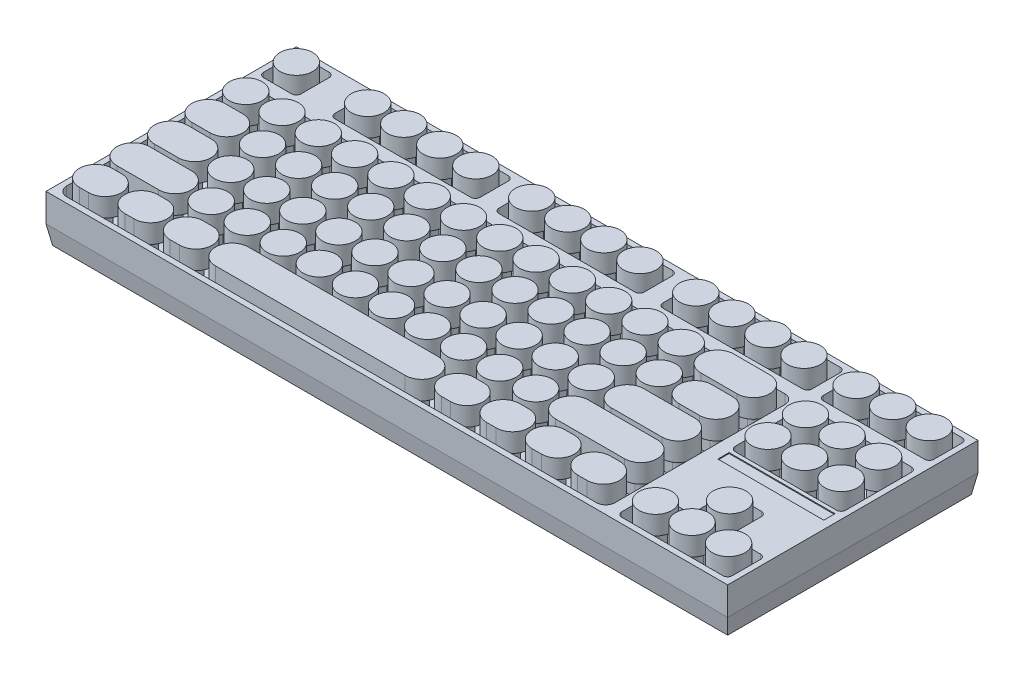
SolidWorks part; units mm, degrees
ref_plane "Front Plane" through (0, 0, 0) normal (0, 0, 1) x (1, 0, 0)
ref_plane "Top Plane" through (0, 0, 0) normal (0, 1, 0) x (1, 0, 0)
ref_plane "Right Plane" through (0, 0, 0) normal (1, 0, 0) x (0, 0, -1)
sketch "Sketch1" plane through (0, 0, 0) normal (0, 1, 0) x (1, 0, 0)
  line L1 (180, 65) -> (-180, 65)
  line L2 (180, 65) -> (180, -65)
  line L3 (180, -65) -> (-180, -65)
  line L4 (-180, 65) -> (-180, -65)
  line L5 (180, 65) -> (-180, -65) construction
  line L6 (180, -65) -> (-180, 65) construction
  point P0 (0, 0)
  dimension "D1" = 360
  dimension "D2" = 130
extrude "Boss-Extrude1" add sketch "Sketch1" along normal blind 10
draft "Draft1" type of draft neutral plane draft angle 10 faces to draft 4 face at (180, 5, 0) face at (0, 5, -65) face at (-180, 5, 0) face at (0, 5, 65) neutral plane through (0, 0, 0) neutral plane normal (0, -1, 0) parameters "D1"=10
sketch "Sketch2" plane through (0, 10, 0) normal (0, 1, 0) x (1, 0, 0)
  line L0 (111.2633, 63.7633) -> (36.7667, 63.7633)
  line L1 (113.7633, 61.2633) -> (113.7633, 46.2633)
  line L2 (111.2633, 43.7633) -> (36.7667, 43.7633)
  line L3 (34.2667, 61.2633) -> (34.2667, 46.2633)
  line L4 (176.2633, 63.7633) -> (122.2633, 63.7633)
  line L5 (176.2633, -43.7633) -> (122.2633, -43.7633) construction
  line L6 (178.7633, -46.2633) -> (178.7633, -61.2633)
  line L7 (176.2633, -63.7633) -> (122.2633, -63.7633)
  line L8 (119.7633, -46.2633) -> (119.7633, -61.2633)
  line L9 (178.7633, -43.7633) -> (119.7633, -63.7633) construction
  line L10 (178.7633, -63.7633) -> (119.7633, -43.7633) construction
  line L11 (156.7633, -23.7633) -> (141.7633, -23.7633)
  line L12 (159.2633, -26.2633) -> (159.2633, -41.2633)
  line L13 (159.2633, -43.7633) -> (139.2633, -43.7633) construction
  line L14 (139.2633, -26.2633) -> (139.2633, -41.2633)
  line L15 (159.2633, -23.7633) -> (139.2633, -43.7633) construction
  line L16 (-178.7633, 66.7633) -> (-178.7633, -66.7633)
  line L17 (-178.7633, 31.7633) -> (-178.7633, -58.7633)
  line L18 (159.2633, -43.7633) -> (139.2633, -23.7633) construction
  line L19 (181.7633, 36.7633) -> (-181.7633, 36.7633)
  line L20 (108.7633, 36.7633) -> (-173.7633, 36.7633)
  line L21 (178.7633, 61.2633) -> (178.7633, 46.2633)
  line L22 (113.7633, -66.7633) -> (113.7633, 66.7633)
  line L23 (113.7633, -58.7633) -> (113.7633, 31.7633)
  line L24 (176.2633, 43.7633) -> (122.2633, 43.7633)
  line L25 (-181.7633, -63.7633) -> (181.7633, -63.7633)
  line L26 (-173.7633, -63.7633) -> (108.7633, -63.7633)
  line L27 (-181.7633, 66.7633) -> (-181.7633, -66.7633) construction
  line L28 (-161.2633, 63.7633) -> (-176.2633, 63.7633)
  line L29 (-158.7633, 61.2633) -> (-158.7633, 46.2633)
  line L30 (-161.2633, 43.7633) -> (-176.2633, 43.7633)
  line L31 (-178.7633, 61.2633) -> (-178.7633, 46.2633)
  line L32 (-158.7633, 63.7633) -> (-178.7633, 43.7633) construction
  line L33 (-158.7633, 43.7633) -> (-178.7633, 63.7633) construction
  line L34 (181.7633, 66.7633) -> (-181.7633, 66.7633) construction
  line L35 (-181.7633, -66.7633) -> (181.7633, -66.7633) construction
  line L36 (-65.7333, 63.7633) -> (-138.2333, 63.7633)
  line L37 (-63.2333, 61.2633) -> (-63.2333, 46.2633)
  line L38 (-65.7333, 43.7633) -> (-138.2333, 43.7633)
  line L39 (-140.7333, 61.2633) -> (-140.7333, 46.2633)
  line L40 (-63.2333, 63.7633) -> (-140.7333, 43.7633) construction
  line L41 (-63.2333, 43.7633) -> (-140.7333, 63.7633) construction
  line L42 (181.7633, -66.7633) -> (181.7633, 66.7633) construction
  line L43 (-181.7633, 66.7633) -> (-181.7633, -66.7633)
  line L44 (-181.7633, -66.7633) -> (181.7633, -66.7633)
  line L45 (181.7633, -66.7633) -> (181.7633, 66.7633)
  line L46 (181.7633, 66.7633) -> (-181.7633, 66.7633)
  line L47 (21.7667, 63.7633) -> (-50.7333, 63.7633)
  line L48 (24.2667, 61.2633) -> (24.2667, 46.2633)
  line L49 (21.7667, 43.7633) -> (-50.7333, 43.7633)
  line L50 (-53.2333, 61.2633) -> (-53.2333, 46.2633)
  line L51 (119.7633, 61.2633) -> (119.7633, 46.2633)
  line L52 (122.2633, -43.7633) -> (136.7633, -43.7633)
  line L53 (176.2633, 36.7633) -> (122.2633, 36.7633)
  line L54 (178.7633, 34.2633) -> (178.7633, -0.7367)
  line L55 (176.2633, -3.2367) -> (122.2633, -3.2367)
  line L56 (119.7633, 34.2633) -> (119.7633, -0.7367)
  line L57 (178.7633, 36.7633) -> (119.7633, -3.2367) construction
  line L58 (178.7633, -3.2367) -> (119.7633, 36.7633) construction
  line L59 (176.2633, -43.7633) -> (161.7633, -43.7633)
  arc A0 (108.7633, -63.7633) -> (113.7633, -58.7633) centre (108.7633, -58.7633) ccw
  arc A1 (113.7633, 31.7633) -> (108.7633, 36.7633) centre (108.7633, 31.7633) ccw
  arc A2 (-173.7633, -63.7633) -> (-178.7633, -58.7633) centre (-173.7633, -58.7633) cw
  arc A3 (-178.7633, 31.7633) -> (-173.7633, 36.7633) centre (-173.7633, 31.7633) cw
  arc A4 (178.7633, -61.2633) -> (176.2633, -63.7633) centre (176.2633, -61.2633) cw
  arc A5 (176.2633, -43.7633) -> (178.7633, -46.2633) centre (176.2633, -46.2633) cw
  arc A6 (122.2633, -43.7633) -> (119.7633, -46.2633) centre (122.2633, -46.2633) ccw
  arc A7 (122.2633, -63.7633) -> (119.7633, -61.2633) centre (122.2633, -61.2633) cw
  arc A8 (156.7633, -23.7633) -> (159.2633, -26.2633) centre (156.7633, -26.2633) cw
  arc A9 (141.7633, -23.7633) -> (139.2633, -26.2633) centre (141.7633, -26.2633) ccw
  arc A10 (178.7633, -0.7367) -> (176.2633, -3.2367) centre (176.2633, -0.7367) cw
  arc A11 (122.2633, -3.2367) -> (119.7633, -0.7367) centre (122.2633, -0.7367) cw
  arc A12 (122.2633, 36.7633) -> (119.7633, 34.2633) centre (122.2633, 34.2633) ccw
  arc A13 (176.2633, 36.7633) -> (178.7633, 34.2633) centre (176.2633, 34.2633) cw
  arc A14 (178.7633, 46.2633) -> (176.2633, 43.7633) centre (176.2633, 46.2633) cw
  arc A15 (176.2633, 63.7633) -> (178.7633, 61.2633) centre (176.2633, 61.2633) cw
  arc A16 (122.2633, 63.7633) -> (119.7633, 61.2633) centre (122.2633, 61.2633) ccw
  arc A17 (122.2633, 43.7633) -> (119.7633, 46.2633) centre (122.2633, 46.2633) cw
  arc A18 (113.7633, 46.2633) -> (111.2633, 43.7633) centre (111.2633, 46.2633) cw
  arc A19 (111.2633, 63.7633) -> (113.7633, 61.2633) centre (111.2633, 61.2633) cw
  arc A20 (36.7667, 63.7633) -> (34.2667, 61.2633) centre (36.7667, 61.2633) ccw
  arc A21 (36.7667, 43.7633) -> (34.2667, 46.2633) centre (36.7667, 46.2633) cw
  arc A22 (24.2667, 46.2633) -> (21.7667, 43.7633) centre (21.7667, 46.2633) cw
  arc A23 (21.7667, 63.7633) -> (24.2667, 61.2633) centre (21.7667, 61.2633) cw
  arc A24 (-50.7333, 43.7633) -> (-53.2333, 46.2633) centre (-50.7333, 46.2633) cw
  arc A25 (-50.7333, 63.7633) -> (-53.2333, 61.2633) centre (-50.7333, 61.2633) ccw
  arc A26 (-63.2333, 46.2633) -> (-65.7333, 43.7633) centre (-65.7333, 46.2633) cw
  arc A27 (-65.7333, 63.7633) -> (-63.2333, 61.2633) centre (-65.7333, 61.2633) cw
  arc A28 (-138.2333, 43.7633) -> (-140.7333, 46.2633) centre (-138.2333, 46.2633) cw
  arc A29 (-138.2333, 63.7633) -> (-140.7333, 61.2633) centre (-138.2333, 61.2633) ccw
  arc A30 (-158.7633, 46.2633) -> (-161.2633, 43.7633) centre (-161.2633, 46.2633) cw
  arc A31 (-176.2633, 43.7633) -> (-178.7633, 46.2633) centre (-176.2633, 46.2633) cw
  arc A32 (-176.2633, 63.7633) -> (-178.7633, 61.2633) centre (-176.2633, 61.2633) ccw
  arc A33 (-161.2633, 63.7633) -> (-158.7633, 61.2633) centre (-161.2633, 61.2633) cw
  arc A34 (136.7633, -43.7633) -> (139.2633, -41.2633) centre (136.7633, -41.2633) ccw
  arc A35 (159.2633, -41.2633) -> (161.7633, -43.7633) centre (161.7633, -41.2633) ccw
  point P22 (-168.7633, 53.7633)
  point P30 (-101.9833, 53.7633)
  point P42 (149.2633, -53.7633)
  point P47 (149.2633, -33.7633)
  point P57 (149.2633, 16.7633)
  point P94 (178.7633, 43.7633)
  point P97 (178.7633, 63.7633)
  point P104 (113.7633, 43.7633)
  point P107 (113.7633, 63.7633)
  point P110 (34.2667, 63.7633)
  point P115 (24.2667, 43.7633)
  point P118 (24.2667, 63.7633)
  point P123 (-53.2333, 63.7633)
  dimension "D5" = 5
  dimension "D34" = 2.5
  dimension "D35" = 2.5
  dimension "D6" = 20
  dimension "D7" = 3
  dimension "D8" = 3
  dimension "D9" = 18.03
  dimension "D10" = 77.5
  dimension "D11" = 20
  dimension "D12" = 3
  dimension "D13" = 10
  dimension "D14" = 3
  dimension "D15" = 20
  dimension "D16" = 77.5
  dimension "D18" = 20
  dimension "D19" = 3
  dimension "D20" = 10
  dimension "D21" = 3
  dimension "D22" = 6
  dimension "D23" = 3
  dimension "D24" = 20
  dimension "D25" = 20
  dimension "D26" = 20
  dimension "D28" = 20
  dimension "D29" = 3
  dimension "D30" = 3
  dimension "D31" = 40
  dimension "D32" = 3
  dimension "D33" = 6
  dimension "D1" = 3
  dimension "D2" = 30
  dimension "D3" = 68
  dimension "D4" = 3
extrude "Boss-Extrude2" add sketch "Sketch2" along normal blind 15
sketch "Sketch3" plane through (0, 10, 0) normal (0, 1, 0) x (1, 0, 0)
  line L0 (-178.031, 63.031) -> (-159.4955, 44.4955) construction
  line L1 (-178.031, 44.4955) -> (-159.4955, 63.031) construction
  line L2 (178.7633, 46.2633) -> (178.7633, 61.2633) construction
  line L3 (-63.2333, 46.2633) -> (-63.2333, 61.2633) construction
  line L4 (176.2633, 36.7633) -> (122.2633, 36.7633) construction
  line L5 (-140.7333, 61.2633) -> (-140.7333, 46.2633) construction
  line L6 (178.7633, 16.7633) -> (119.7633, 16.7633) construction
  line L7 (178.7633, -0.7367) -> (178.7633, 34.2633) construction
  line L8 (119.7633, 34.2633) -> (119.7633, -0.7367) construction
  line L9 (90.9667, 6.7633) -> (101.9567, 6.7633) construction
  line L10 (-168.7633, 6.7633) -> (-159.0233, 6.7633) construction
  line L11 (-168.7633, 9.7633) -> (-159.0233, 9.7633)
  line L12 (-168.7633, 3.7633) -> (-159.0233, 3.7633)
  line L13 (-168.7633, -13.2367) -> (-156.0233, -13.2367) construction
  line L14 (-53.2333, 61.2633) -> (-53.2333, 46.2633) construction
  line L15 (34.2667, 61.2633) -> (34.2667, 46.2633) construction
  line L16 (119.7633, 61.2633) -> (119.7633, 46.2633) construction
  line L17 (-168.7633, -10.2367) -> (-156.0233, -10.2367)
  line L18 (-168.7633, -16.2367) -> (-156.0233, -16.2367)
  line L19 (-168.7633, -33.2367) -> (-146.4083, -33.2367) construction
  line L20 (-168.7633, -30.2367) -> (-146.4083, -30.2367)
  line L21 (-168.7633, -36.2367) -> (-146.4083, -36.2367)
  line L22 (82.7267, 26.7633) -> (101.9567, 26.7633) construction
  line L23 (82.7267, 29.7633) -> (101.9567, 29.7633)
  line L24 (82.7267, 23.7633) -> (101.9567, 23.7633)
  line L25 (90.9667, 9.7633) -> (101.9567, 9.7633)
  line L26 (90.9667, 3.7633) -> (101.9567, 3.7633)
  line L27 (74.7367, -13.2367) -> (101.9567, -13.2367) construction
  line L28 (74.7367, -10.2367) -> (101.9567, -10.2367)
  line L29 (74.7367, -16.2367) -> (101.9567, -16.2367)
  line L30 (65.1217, -33.2367) -> (101.9567, -33.2367) construction
  line L31 (65.1217, -30.2367) -> (101.9567, -30.2367)
  line L32 (65.1217, -36.2367) -> (101.9567, -36.2367)
  line L33 (-168.7633, -53.2367) -> (-163.7633, -53.2367) construction
  line L34 (-168.7633, -50.2367) -> (-163.7633, -50.2367)
  line L35 (-168.7633, -56.2367) -> (-163.7633, -56.2367)
  line L36 (-144.5333, -53.2367) -> (-139.5333, -53.2367) construction
  line L37 (-144.5333, -50.2367) -> (-139.5333, -50.2367)
  line L38 (-144.5333, -56.2367) -> (-139.5333, -56.2367)
  line L39 (-120.3033, -53.2367) -> (-115.3033, -53.2367) construction
  line L40 (-120.3033, -50.2367) -> (-115.3033, -50.2367)
  line L41 (-120.3033, -56.2367) -> (-115.3033, -56.2367)
  line L42 (96.9567, -53.2367) -> (101.9567, -53.2367) construction
  line L43 (96.9567, -50.2367) -> (101.9567, -50.2367)
  line L44 (96.9567, -56.2367) -> (101.9567, -56.2367)
  line L45 (72.7267, -50.2367) -> (77.7267, -50.2367)
  line L46 (72.7267, -56.2367) -> (77.7267, -56.2367)
  line L47 (72.7267, -53.2367) -> (77.7267, -53.2367) construction
  line L48 (48.4967, -50.2367) -> (53.4967, -50.2367)
  line L49 (48.4967, -56.2367) -> (53.4967, -56.2367)
  line L50 (48.4967, -53.2367) -> (53.4967, -53.2367) construction
  line L51 (24.2667, -50.2367) -> (29.2667, -50.2367)
  line L52 (24.2667, -56.2367) -> (29.2667, -56.2367)
  line L53 (24.2667, -53.2367) -> (29.2667, -53.2367) construction
  line L54 (-96.0733, -53.2367) -> (5.0367, -53.2367) construction
  line L55 (-96.0733, -50.2367) -> (5.0367, -50.2367)
  line L56 (-96.0733, -56.2367) -> (5.0367, -56.2367)
  arc A0 (-176.2633, 63.7633) -> (-178.7633, 61.2633) centre (-176.2633, 61.2633) ccw construction
  arc A1 (-161.2633, 43.7633) -> (-158.7633, 46.2633) centre (-161.2633, 46.2633) ccw construction
  arc A2 (-178.7633, 46.2633) -> (-176.2633, 43.7633) centre (-176.2633, 46.2633) ccw construction
  arc A3 (-158.7633, 61.2633) -> (-161.2633, 63.7633) centre (-161.2633, 61.2633) ccw construction
  circle A4 centre (-168.7633, 53.7633) radius 4.5
  circle A5 centre (-130.7333, 53.7633) radius 4.5
  circle A6 centre (-111.5083, 53.7633) radius 4.5
  circle A7 centre (-92.4583, 53.7633) radius 4.5
  circle A8 centre (-73.2333, 53.7633) radius 4.5
  circle A43 centre (-43.2333, 53.7633) radius 4.5
  circle A44 centre (44.2667, 53.7633) radius 4.5
  circle A45 centre (129.7633, 53.7633) radius 4.5
  circle A46 centre (-24.0033, 53.7633) radius 4.5
  circle A47 centre (-4.7733, 53.7633) radius 4.5
  circle A48 centre (14.4567, 53.7633) radius 4.5
  circle A49 centre (63.4967, 53.7633) radius 4.5
  circle A50 centre (82.7267, 53.7633) radius 4.5
  circle A51 centre (101.9567, 53.7633) radius 4.5
  circle A52 centre (168.7633, 53.7633) radius 4.5
  circle A53 centre (149.2633, 53.7633) radius 4.5
  circle A54 centre (129.7633, 26.7633) radius 4.5
  circle A55 centre (149.2633, 26.7633) radius 4.5
  circle A56 centre (168.7633, 26.7633) radius 4.5
  circle A57 centre (168.7633, 6.7633) radius 4.5
  circle A58 centre (149.2633, 6.7633) radius 4.5
  circle A59 centre (129.7633, 6.7633) radius 4.5
  circle A60 centre (63.4967, 26.7633) radius 4.5
  circle A61 centre (44.1417, 26.7633) radius 4.5
  circle A62 centre (24.7867, 26.7633) radius 4.5
  circle A63 centre (5.4317, 26.7633) radius 4.5
  circle A64 centre (-13.9233, 26.7633) radius 4.5
  circle A65 centre (-33.2783, 26.7633) radius 4.5
  circle A66 centre (-52.6333, 26.7633) radius 4.5
  circle A67 centre (-71.9883, 26.7633) radius 4.5
  circle A68 centre (-91.3433, 26.7633) radius 4.5
  circle A69 centre (-110.6983, 26.7633) radius 4.5
  circle A70 centre (-130.0533, 26.7633) radius 4.5
  circle A71 centre (-149.4083, 26.7633) radius 4.5
  circle A72 centre (-168.7633, 26.7633) radius 4.5
  circle A73 centre (129.7633, -53.2367) radius 4.5
  circle A74 centre (149.2633, -53.2367) radius 4.5
  circle A75 centre (168.7633, -53.2367) radius 4.5
  circle A76 centre (149.2633, -33.2367) radius 4.5
  circle A78 centre (-139.7933, 6.7633) radius 4.5
  circle A90 centre (-120.5633, 6.7633) radius 4.5
  circle A91 centre (-101.3333, 6.7633) radius 4.5
  circle A92 centre (-82.1033, 6.7633) radius 4.5
  circle A93 centre (-62.8733, 6.7633) radius 4.5
  circle A94 centre (-43.6433, 6.7633) radius 4.5
  circle A95 centre (-24.4133, 6.7633) radius 4.5
  circle A96 centre (-5.1833, 6.7633) radius 4.5
  circle A97 centre (14.0467, 6.7633) radius 4.5
  circle A98 centre (33.2767, 6.7633) radius 4.5
  circle A99 centre (52.5067, 6.7633) radius 4.5
  circle A100 centre (71.7367, 6.7633) radius 4.5
  circle A101 centre (-136.7933, -13.2367) radius 4.5
  circle A102 centre (-117.5633, -13.2367) radius 4.5
  circle A103 centre (-98.3333, -13.2367) radius 4.5
  circle A104 centre (-79.1033, -13.2367) radius 4.5
  circle A105 centre (-59.8733, -13.2367) radius 4.5
  circle A106 centre (-40.6433, -13.2367) radius 4.5
  circle A107 centre (-21.4133, -13.2367) radius 4.5
  circle A108 centre (-2.1833, -13.2367) radius 4.5
  circle A109 centre (17.0467, -13.2367) radius 4.5
  circle A110 centre (36.2767, -13.2367) radius 4.5
  circle A111 centre (55.5067, -13.2367) radius 4.5
  circle A112 centre (-127.1783, -33.2367) radius 4.5
  circle A113 centre (-107.9483, -33.2367) radius 4.5
  circle A114 centre (-88.7183, -33.2367) radius 4.5
  circle A115 centre (-69.4883, -33.2367) radius 4.5
  circle A116 centre (-50.2583, -33.2367) radius 4.5
  circle A117 centre (-31.0283, -33.2367) radius 4.5
  circle A118 centre (-11.7983, -33.2367) radius 4.5
  circle A119 centre (7.4317, -33.2367) radius 4.5
  circle A120 centre (26.6617, -33.2367) radius 4.5
  circle A121 centre (45.8917, -33.2367) radius 4.5
  arc A122 (-168.7633, 9.7633) -> (-168.7633, 3.7633) centre (-168.7633, 6.7633) ccw
  arc A123 (-159.0233, 3.7633) -> (-159.0233, 9.7633) centre (-159.0233, 6.7633) ccw
  arc A124 (-168.7633, -10.2367) -> (-168.7633, -16.2367) centre (-168.7633, -13.2367) ccw
  arc A125 (-156.0233, -16.2367) -> (-156.0233, -10.2367) centre (-156.0233, -13.2367) ccw
  arc A126 (-168.7633, -30.2367) -> (-168.7633, -36.2367) centre (-168.7633, -33.2367) ccw
  arc A127 (-146.4083, -36.2367) -> (-146.4083, -30.2367) centre (-146.4083, -33.2367) ccw
  arc A128 (82.7267, 29.7633) -> (82.7267, 23.7633) centre (82.7267, 26.7633) ccw
  arc A129 (101.9567, 23.7633) -> (101.9567, 29.7633) centre (101.9567, 26.7633) ccw
  arc A130 (90.9667, 9.7633) -> (90.9667, 3.7633) centre (90.9667, 6.7633) ccw
  arc A131 (101.9567, 3.7633) -> (101.9567, 9.7633) centre (101.9567, 6.7633) ccw
  arc A132 (74.7367, -10.2367) -> (74.7367, -16.2367) centre (74.7367, -13.2367) ccw
  arc A133 (101.9567, -16.2367) -> (101.9567, -10.2367) centre (101.9567, -13.2367) ccw
  arc A134 (65.1217, -30.2367) -> (65.1217, -36.2367) centre (65.1217, -33.2367) ccw
  arc A135 (101.9567, -36.2367) -> (101.9567, -30.2367) centre (101.9567, -33.2367) ccw
  arc A136 (-168.7633, -50.2367) -> (-168.7633, -56.2367) centre (-168.7633, -53.2367) ccw
  arc A137 (-163.7633, -56.2367) -> (-163.7633, -50.2367) centre (-163.7633, -53.2367) ccw
  arc A138 (-144.5333, -50.2367) -> (-144.5333, -56.2367) centre (-144.5333, -53.2367) ccw
  arc A139 (-139.5333, -56.2367) -> (-139.5333, -50.2367) centre (-139.5333, -53.2367) ccw
  arc A140 (-120.3033, -50.2367) -> (-120.3033, -56.2367) centre (-120.3033, -53.2367) ccw
  arc A141 (-115.3033, -56.2367) -> (-115.3033, -50.2367) centre (-115.3033, -53.2367) ccw
  arc A142 (96.9567, -50.2367) -> (96.9567, -56.2367) centre (96.9567, -53.2367) ccw
  arc A143 (101.9567, -56.2367) -> (101.9567, -50.2367) centre (101.9567, -53.2367) ccw
  arc A144 (77.7267, -56.2367) -> (77.7267, -50.2367) centre (77.7267, -53.2367) ccw
  arc A145 (72.7267, -50.2367) -> (72.7267, -56.2367) centre (72.7267, -53.2367) ccw
  arc A146 (53.4967, -56.2367) -> (53.4967, -50.2367) centre (53.4967, -53.2367) ccw
  arc A147 (48.4967, -50.2367) -> (48.4967, -56.2367) centre (48.4967, -53.2367) ccw
  arc A148 (29.2667, -56.2367) -> (29.2667, -50.2367) centre (29.2667, -53.2367) ccw
  arc A149 (24.2667, -50.2367) -> (24.2667, -56.2367) centre (24.2667, -53.2367) ccw
  arc A150 (-96.0733, -50.2367) -> (-96.0733, -56.2367) centre (-96.0733, -53.2367) ccw
  arc A151 (5.0367, -56.2367) -> (5.0367, -50.2367) centre (5.0367, -53.2367) ccw
  point P113 (-163.8933, 6.7633)
  point P187 (-162.3933, -13.2367)
  point P194 (-166.2633, -53.2367)
  point P196 (-157.5858, -33.2367)
  point P203 (92.3417, 26.7633)
  point P212 (96.4617, 6.7633)
  point P220 (88.3467, -13.2367)
  point P227 (-142.0333, -53.2367)
  point P228 (99.4567, -53.2367)
  point P229 (83.5392, -33.2367)
  point P244 (-117.8033, -53.2367)
  point P257 (75.2267, -53.2367)
  point P265 (50.9967, -53.2367)
  point P272 (26.7667, -53.2367)
  point P280 (-45.5183, -53.2367)
  dimension "D1" = 9
  dimension "D30" = 3
  dimension "D34" = 3
  dimension "D35" = 3
  dimension "D37" = 3
  dimension "D39" = 3
  dimension "D41" = 3
  dimension "D43" = 3
  dimension "D44" = 3
  dimension "D46" = 3
  dimension "D48" = 3
  dimension "D51" = 3
  dimension "D2" = 10
  dimension "D3" = 10
  dimension "D4" = 19.225
  dimension "D5" = 19.225
  dimension "D6" = 10
  dimension "D7" = 10
  dimension "D8" = 10
  dimension "D9" = 19.23
  dimension "D10" = 19.23
  dimension "D11" = 10
  dimension "D12" = 19.5
  dimension "D13" = 10
  dimension "D14" = 19.5
  dimension "D15" = 3
  dimension "D16" = 4
  dimension "D17" = 20
  dimension "D18" = 10
  dimension "D19" = 3
  dimension "D20" = 13
  dimension "D21" = 20
  dimension "D22" = 9.615
  dimension "D23" = 19.23
  dimension "D24" = 12
  dimension "D26" = 3
  dimension "D25" = 20
  dimension "D27" = 19.23
  dimension "D29" = 9.615
  dimension "D31" = 9.615
  dimension "D32" = 19.23
  dimension "D33" = 19.23
  dimension "D36" = 19.23
  dimension "D38" = 19.23
  dimension "D40" = 19.23
  dimension "D42" = 19.23
  dimension "D45" = 5
  dimension "D47" = 19.23
  dimension "D49" = 5
  dimension "D50" = 19.23
  dimension "D52" = 19.23
  dimension "D53" = 19.23
  dimension "D28" = 11
extrude "Boss-Extrude3" add sketch "Sketch3" along normal blind 15
sketch "Sketch4" plane through (0, 25, 0) normal (0, 1, 0) x (1, 0, 0)
  line L0 (-168.7633, 6.7633) -> (-159.0233, 6.7633) construction
  line L3 (-168.7633, 15.5133) -> (-159.0233, 15.5133)
  line L4 (-168.7633, -1.9867) -> (-159.0233, -1.9867)
  line L5 (-168.7633, -13.2367) -> (-156.0233, -13.2367) construction
  line L6 (-168.7633, -4.4867) -> (-156.0233, -4.4867)
  line L7 (-168.7633, -21.9867) -> (-156.0233, -21.9867)
  line L8 (-168.7633, -33.2367) -> (-146.4083, -33.2367) construction
  line L9 (-168.7633, -24.4867) -> (-146.4083, -24.4867)
  line L10 (-168.7633, -41.9867) -> (-146.4083, -41.9867)
  line L11 (82.7267, 26.7633) -> (101.9567, 26.7633) construction
  line L12 (82.7267, 35.5133) -> (101.9567, 35.5133)
  line L13 (82.7267, 18.0133) -> (101.9567, 18.0133)
  line L14 (90.9667, 6.7633) -> (101.9567, 6.7633) construction
  line L15 (90.9667, 15.5133) -> (101.9567, 15.5133)
  line L16 (90.9667, -1.9867) -> (101.9567, -1.9867)
  line L17 (74.7367, -13.2367) -> (101.9567, -13.2367) construction
  line L18 (74.7367, -4.4867) -> (101.9567, -4.4867)
  line L19 (74.7367, -21.9867) -> (101.9567, -21.9867)
  line L20 (65.1217, -33.2367) -> (101.9567, -33.2367) construction
  line L21 (65.1217, -24.4867) -> (101.9567, -24.4867)
  line L22 (65.1217, -41.9867) -> (101.9567, -41.9867)
  line L23 (-168.7633, -53.2367) -> (-163.7633, -53.2367) construction
  line L24 (-168.7633, -44.4867) -> (-163.7633, -44.4867)
  line L25 (-168.7633, -61.9867) -> (-163.7633, -61.9867)
  line L26 (-144.5333, -61.9867) -> (-139.5333, -61.9867)
  line L29 (-144.5333, -44.4867) -> (-139.5333, -44.4867)
  line L30 (-144.5333, -53.2367) -> (-139.5333, -53.2367) construction
  line L31 (-120.3033, -61.9867) -> (-115.3033, -61.9867)
  line L32 (-120.3033, -44.4867) -> (-115.3033, -44.4867)
  line L33 (-120.3033, -53.2367) -> (-115.3033, -53.2367) construction
  line L34 (96.9567, -61.9867) -> (101.9567, -61.9867)
  line L35 (96.9567, -44.4867) -> (101.9567, -44.4867)
  line L36 (96.9567, -53.2367) -> (101.9567, -53.2367) construction
  line L37 (72.7267, -44.4867) -> (77.7267, -44.4867)
  line L38 (72.7267, -61.9867) -> (77.7267, -61.9867)
  line L39 (72.7267, -53.2367) -> (77.7267, -53.2367) construction
  line L40 (48.4967, -44.4867) -> (53.4967, -44.4867)
  line L41 (48.4967, -61.9867) -> (53.4967, -61.9867)
  line L42 (48.4967, -53.2367) -> (53.4967, -53.2367) construction
  line L43 (24.2667, -44.4867) -> (29.2667, -44.4867)
  line L44 (24.2667, -61.9867) -> (29.2667, -61.9867)
  line L45 (24.2667, -53.2367) -> (29.2667, -53.2367) construction
  line L46 (-96.0733, -53.2367) -> (5.0367, -53.2367) construction
  line L47 (-96.0733, -44.4867) -> (5.0367, -44.4867)
  line L48 (-96.0733, -61.9867) -> (5.0367, -61.9867)
  circle A0 centre (-168.7633, 53.7633) radius 8.75
  circle A1 centre (-130.7333, 53.7633) radius 8.75
  circle A2 centre (-111.5083, 53.7633) radius 8.75
  circle A3 centre (-92.2833, 53.7633) radius 8.75
  circle A4 centre (-73.0583, 53.7633) radius 8.75
  circle A5 centre (-43.2333, 53.7633) radius 8.75
  circle A6 centre (-24.0033, 53.7633) radius 8.75
  circle A7 centre (-4.7733, 53.7633) radius 8.75
  circle A8 centre (14.4567, 53.7633) radius 8.75
  circle A9 centre (44.2667, 53.7633) radius 8.75
  circle A10 centre (63.4967, 53.7633) radius 8.75
  circle A11 centre (82.7267, 53.7633) radius 8.75
  circle A12 centre (101.9567, 53.7633) radius 8.75
  circle A13 centre (129.7633, 53.7633) radius 8.75
  circle A16 centre (149.2633, 53.7633) radius 8.75
  circle A17 centre (168.7633, 53.7633) radius 8.75
  circle A18 centre (63.4967, 26.7633) radius 8.75
  circle A19 centre (44.1417, 26.7633) radius 8.75
  circle A20 centre (24.7867, 26.7633) radius 8.75
  circle A21 centre (5.4317, 26.7633) radius 8.75
  circle A22 centre (-13.9233, 26.7633) radius 8.75
  circle A23 centre (-33.2783, 26.7633) radius 8.75
  circle A24 centre (-52.6333, 26.7633) radius 8.75
  circle A25 centre (-71.9883, 26.7633) radius 8.75
  circle A26 centre (-91.3433, 26.7633) radius 8.75
  circle A27 centre (-110.6983, 26.7633) radius 8.75
  circle A28 centre (-130.0533, 26.7633) radius 8.75
  circle A29 centre (-149.4083, 26.7633) radius 8.75
  circle A30 centre (-168.7633, 26.7633) radius 8.75
  circle A31 centre (71.7367, 6.7633) radius 8.75
  circle A32 centre (52.5067, 6.7633) radius 8.75
  circle A33 centre (33.2767, 6.7633) radius 8.75
  circle A34 centre (14.0467, 6.7633) radius 8.75
  circle A35 centre (-5.1833, 6.7633) radius 8.75
  circle A36 centre (-24.4133, 6.7633) radius 8.75
  circle A37 centre (-43.6433, 6.7633) radius 8.75
  circle A38 centre (-62.8733, 6.7633) radius 8.75
  circle A39 centre (-82.1033, 6.7633) radius 8.75
  circle A40 centre (-101.3333, 6.7633) radius 8.75
  circle A41 centre (-120.5633, 6.7633) radius 8.75
  circle A42 centre (-139.7933, 6.7633) radius 8.75
  circle A44 centre (129.7633, 26.7633) radius 8.75
  circle A45 centre (129.7633, 6.7633) radius 8.75
  circle A48 centre (168.7633, 26.7633) radius 8.75
  circle A49 centre (168.7633, 6.7633) radius 8.75
  circle A50 centre (149.2633, 26.7633) radius 8.75 [skipped]
  circle A51 centre (149.2633, 6.7633) radius 8.75 [skipped]
  circle A52 centre (149.2633, 26.7633) radius 8.75
  circle A53 centre (149.2633, 6.7633) radius 8.75
  circle A54 centre (-159.0233, 6.7633) radius 8.75 [skipped]
  circle A55 centre (129.7633, -53.2367) radius 8.75
  circle A56 centre (149.2633, -33.2367) radius 8.75
  circle A57 centre (149.2633, -53.2367) radius 8.75
  circle A58 centre (168.7633, -53.2367) radius 8.75
  circle A59 centre (-136.7933, -13.2367) radius 8.75
  circle A60 centre (-117.5633, -13.2367) radius 8.75
  circle A61 centre (-98.3333, -13.2367) radius 8.75
  circle A62 centre (-79.1033, -13.2367) radius 8.75
  circle A63 centre (-59.8733, -13.2367) radius 8.75
  circle A64 centre (-40.6433, -13.2367) radius 8.75
  circle A65 centre (-21.4133, -13.2367) radius 8.75
  circle A66 centre (-2.1833, -13.2367) radius 8.75
  circle A67 centre (17.0467, -13.2367) radius 8.75
  circle A68 centre (36.2767, -13.2367) radius 8.75
  circle A69 centre (55.5067, -13.2367) radius 8.75
  circle A70 centre (-127.1783, -33.2367) radius 8.75
  circle A71 centre (-107.9483, -33.2367) radius 8.75
  circle A72 centre (-88.7183, -33.2367) radius 8.75
  circle A73 centre (-69.4883, -33.2367) radius 8.75
  circle A74 centre (-50.2583, -33.2367) radius 8.75
  circle A75 centre (-31.0283, -33.2367) radius 8.75
  circle A76 centre (-11.7983, -33.2367) radius 8.75
  circle A77 centre (7.4317, -33.2367) radius 8.75
  circle A78 centre (26.6617, -33.2367) radius 8.75
  circle A79 centre (45.8917, -33.2367) radius 8.75
  arc A82 (-168.7633, 15.5133) -> (-168.7633, -1.9867) centre (-168.7633, 6.7633) ccw
  arc A83 (-159.0233, -1.9867) -> (-159.0233, 15.5133) centre (-159.0233, 6.7633) ccw
  arc A84 (-168.7633, -4.4867) -> (-168.7633, -21.9867) centre (-168.7633, -13.2367) ccw
  arc A85 (-156.0233, -21.9867) -> (-156.0233, -4.4867) centre (-156.0233, -13.2367) ccw
  arc A86 (-168.7633, -24.4867) -> (-168.7633, -41.9867) centre (-168.7633, -33.2367) ccw
  arc A87 (-146.4083, -41.9867) -> (-146.4083, -24.4867) centre (-146.4083, -33.2367) ccw
  arc A88 (82.7267, 35.5133) -> (82.7267, 18.0133) centre (82.7267, 26.7633) ccw
  arc A89 (101.9567, 18.0133) -> (101.9567, 35.5133) centre (101.9567, 26.7633) ccw
  arc A90 (90.9667, 15.5133) -> (90.9667, -1.9867) centre (90.9667, 6.7633) ccw
  arc A91 (101.9567, -1.9867) -> (101.9567, 15.5133) centre (101.9567, 6.7633) ccw
  arc A92 (74.7367, -4.4867) -> (74.7367, -21.9867) centre (74.7367, -13.2367) ccw
  arc A93 (101.9567, -21.9867) -> (101.9567, -4.4867) centre (101.9567, -13.2367) ccw
  arc A94 (65.1217, -24.4867) -> (65.1217, -41.9867) centre (65.1217, -33.2367) ccw
  arc A95 (101.9567, -41.9867) -> (101.9567, -24.4867) centre (101.9567, -33.2367) ccw
  arc A96 (-168.7633, -44.4867) -> (-168.7633, -61.9867) centre (-168.7633, -53.2367) ccw
  arc A97 (-163.7633, -61.9867) -> (-163.7633, -44.4867) centre (-163.7633, -53.2367) ccw
  arc A100 (-144.5333, -44.4867) -> (-144.5333, -61.9867) centre (-144.5333, -53.2367) ccw
  arc A101 (-139.5333, -61.9867) -> (-139.5333, -44.4867) centre (-139.5333, -53.2367) ccw
  arc A102 (-120.3033, -44.4867) -> (-120.3033, -61.9867) centre (-120.3033, -53.2367) ccw
  arc A103 (-115.3033, -61.9867) -> (-115.3033, -44.4867) centre (-115.3033, -53.2367) ccw
  arc A104 (96.9567, -44.4867) -> (96.9567, -61.9867) centre (96.9567, -53.2367) ccw
  arc A105 (101.9567, -61.9867) -> (101.9567, -44.4867) centre (101.9567, -53.2367) ccw
  arc A106 (77.7267, -61.9867) -> (77.7267, -44.4867) centre (77.7267, -53.2367) ccw
  arc A107 (72.7267, -44.4867) -> (72.7267, -61.9867) centre (72.7267, -53.2367) ccw
  arc A108 (53.4967, -61.9867) -> (53.4967, -44.4867) centre (53.4967, -53.2367) ccw
  arc A109 (48.4967, -44.4867) -> (48.4967, -61.9867) centre (48.4967, -53.2367) ccw
  arc A110 (29.2667, -61.9867) -> (29.2667, -44.4867) centre (29.2667, -53.2367) ccw
  arc A111 (24.2667, -44.4867) -> (24.2667, -61.9867) centre (24.2667, -53.2367) ccw
  arc A112 (-96.0733, -44.4867) -> (-96.0733, -61.9867) centre (-96.0733, -53.2367) ccw
  arc A113 (5.0367, -61.9867) -> (5.0367, -44.4867) centre (5.0367, -53.2367) ccw
  point P99 (-163.8933, 6.7633)
  point P185 (-162.3933, -13.2367)
  point P198 (-157.5858, -33.2367)
  point P207 (92.3417, 26.7633)
  point P212 (96.4617, 6.7633)
  point P221 (88.3467, -13.2367)
  point P230 (83.5392, -33.2367)
  point P243 (-166.2633, -53.2367)
  point P253 (-142.0333, -53.2367)
  point P260 (-117.8033, -53.2367)
  point P268 (99.4567, -53.2367)
  point P275 (75.2267, -53.2367)
  point P279 (-45.5183, -53.2367)
  point P284 (50.9967, -53.2367)
  point P291 (26.7667, -53.2367)
  dimension "D1" = 17.5
  dimension "D2" = 17.5
  dimension "D11" = 8.75
  dimension "D12" = 8.75
  dimension "D13" = 8.75
  dimension "D14" = 8.75
  dimension "D15" = 8.75
  dimension "D16" = 8.75
  dimension "D17" = 8.75
  dimension "D18" = 8.75
  dimension "D19" = 3
  dimension "D20" = 8.75
  dimension "D21" = 8.75
  dimension "D3" = 4
  dimension "D4" = 4
  dimension "D5" = 4
  dimension "D7" = 3
  dimension "D6" = 13
  dimension "D9" = 13
  dimension "D8" = 3
  dimension "D10" = 11
extrude "Boss-Extrude5" add sketch "Sketch4" along normal blind 10 from offset 4 offset against normal yes
sketch "Sketch5" plane through (0, 25, 0) normal (0, 1, 0) x (1, 0, 0)
  line L0 (121.0133, 6.7633) -> (121.0133, -11.2367) construction
  line L1 (121.0133, -5.2367) -> (177.5133, -5.2367)
  line L2 (121.0133, -5.2367) -> (121.0133, -11.2367)
  line L3 (121.0133, -11.2367) -> (177.5133, -11.2367)
  line L4 (177.5133, -5.2367) -> (177.5133, -11.2367)
  line L5 (177.5133, 6.7633) -> (177.5133, -11.2367) construction
  line L6 (122.2633, -3.2367) -> (176.2633, -3.2367) construction
  circle A0 centre (129.7633, 6.7633) radius 8.75 construction
  circle A1 centre (168.7633, 6.7633) radius 8.75 construction
  dimension "D1" = 2
  dimension "D2" = 6
  dimension "D3" = 56.5
extrude "Cut-Extrude1" cut sketch "Sketch5" against normal blind 0.5
sketch "Sketch6" plane through (0, 0, 0) normal (0, -1, 0) x (1, 0, 0)
  line L0 (0, 0) -> (0, -65) construction
  line L1 (180, -65) -> (-180, -65) construction
  line L2 (180, 65) -> (180, -65) construction
  line L3 (155, -35) -> (135, -35)
  line L4 (155, -35) -> (155, -15)
  line L5 (155, -15) -> (135, -15)
  line L6 (135, -35) -> (135, -15)
  line L7 (-155, -15) -> (-135, -15)
  line L8 (-135, -35) -> (-135, -15)
  line L9 (-155, -35) -> (-135, -35)
  line L10 (-155, -35) -> (-155, -15)
  dimension "D1" = 20
  dimension "D2" = 20
  dimension "D3" = 25
  dimension "D4" = 30
extrude "Cut-Extrude2" cut sketch "Sketch6" against normal blind 3
sketch "Sketch7" plane through (0, 0, 0) normal (0, -1, 0) x (1, 0, 0)
  line L0 (-152, 55) -> (-138, 55) construction
  line L1 (-152, 58) -> (-138, 58)
  line L2 (-152, 52) -> (-138, 52)
  line L3 (0, 0) -> (0, 65) construction
  line L4 (-180, 65) -> (180, 65) construction
  line L5 (-180, -65) -> (-180, 65) construction
  line L6 (152, 55) -> (138, 55) construction
  line L7 (152, 58) -> (138, 58)
  line L8 (152, 52) -> (138, 52)
  arc A0 (-152, 58) -> (-152, 52) centre (-152, 55) ccw
  arc A1 (-138, 52) -> (-138, 58) centre (-138, 55) ccw
  arc A2 (152, 58) -> (152, 52) centre (152, 55) cw
  arc A3 (138, 52) -> (138, 58) centre (138, 55) cw
  point P2 (-145, 55)
  point P12 (-155, 55)
  point P17 (145, 55)
  dimension "D2" = 20
  dimension "D1" = 25
  dimension "D3" = 6
  dimension "D4" = 10
extrude "Boss-Extrude6" add sketch "Sketch7" along normal blind 1
sketch "Sketch8" plane through (135, 0, 0) normal (1, 0, 0) x (0, 0, -1)
  line L0 (35, 3) -> (44.1718, -0.1548)
  line L1 (44.0092, -1.1276) -> (35, -1.1276)
  line L2 (35, -1.1276) -> (35, 3)
  arc A0 (44.1718, -0.1548) -> (44.0092, -1.1276) centre (44.0092, -0.6276) cw
  point P6 (47, -1.1276)
  dimension "D2" = 0.5
  dimension "D1" = 12
  dimension "D3" = 71.018
extrude "Cut-Extrude3" cut sketch "Sketch8" along normal up to surface (20 mm away) up to face at (155, 1.5, -25)
extrude "Cut-Extrude4" cut sketch "Sketch8<2>" along direction (-1, 0, 0) on the side against the normal up to surface (290 mm away) from surface up to face at (-155, 1.5, -25) starting at face at (-135, 1.5, -25)
sketch "Sketch8<2>" plane through (135, 0, 0) normal (1, 0, 0) x (0, 0, -1) same geometry as "Sketch8"
sketch "Sketch9" plane through (135, 0, 0) normal (1, 0, 0) x (0, 0, -1)
  line L0 (65, 0) -> (-65, 0) construction
  line L2 (43.7217, 0) -> (45.0332, 0)
  line L3 (-65, 0) -> (65, 0) construction
  arc A0 (43.7217, 0) -> (45.0332, 0) centre (44.3775, 0.2449) ccw
  dimension "D1" = 0.7
  dimension "D2" = 0.6558
extrude "Boss-Extrude7" add sketch "Sketch9" along normal up to surface (20 mm away) up to face at (155, 1.5, -27.1804)
extrude "Boss-Extrude8" add sketch "Sketch9<2>" along direction (1, 0, 0) on the side of the normal up to surface (-270 mm away) from surface up to face at (-135, 1.5, -27.1804) starting at face at (-155, 1.5, -27.1804)
sketch "Sketch9<2>" plane through (135, 0, 0) normal (1, 0, 0) x (0, 0, -1) same geometry as "Sketch9"
sketch "Sketch10" plane through (135, 0, 0) normal (1, 0, 0) x (0, 0, -1)
  line L0 (40.232, 0.6932) -> (54.5491, -3.3681)
  line L2 (53.2926, -3.7264) -> (40.232, 0)
  line L3 (15, 0) -> (43.7217, 0) construction
  line L4 (40.232, 0) -> (40.232, 0.6932)
  line L5 (53.2926, -3.7264) -> (54.5491, -3.7594)
  line L6 (54.5491, -3.3681) -> (54.5491, -3.5489)
  line L8 (54.5491, -3.7594) -> (54.5491, -3.5489)
  point P2 (0, 0)
extrude "Boss-Extrude12" add sketch "Sketch10" along normal up to surface (20 mm away) separate body up to face at (155, 1.5, -27.1804)
extrude "Boss-Extrude13" add sketch "Sketch10<3>" along normal up to surface (-270 mm away) from surface separate body up to face at (-135, 1.5, -27.1804) starting at face at (-155, 1.5, -27.1804)
sketch "Sketch10<3>" plane through (135, 0, 0) normal (1, 0, 0) x (0, 0, -1) same geometry as "Sketch10"
